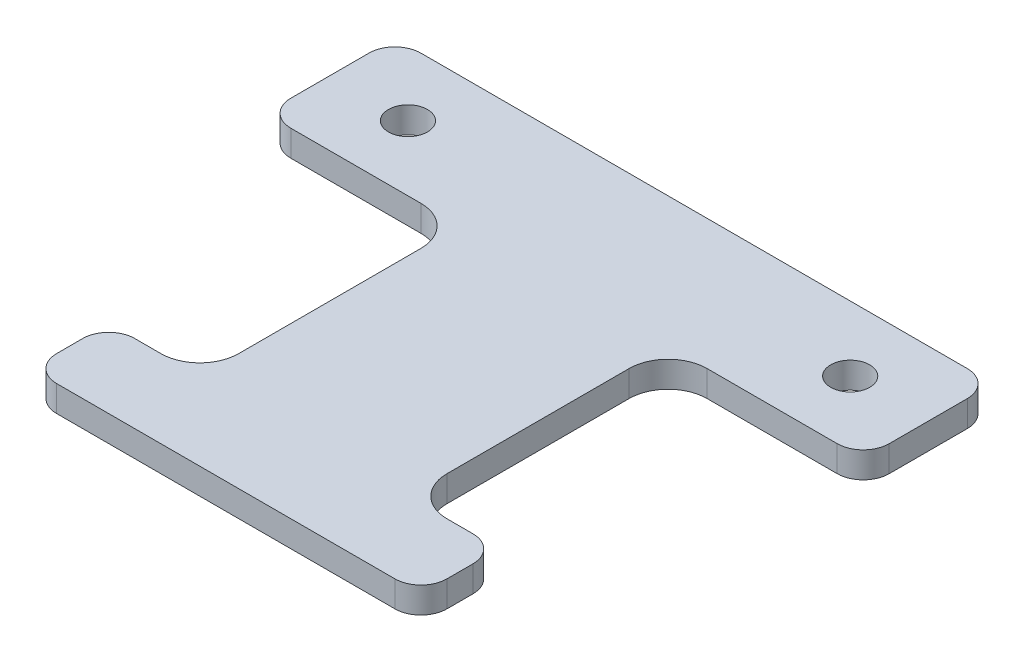
SolidWorks part; units mm, degrees
ref_plane "Vorne" through (0, 0, 0) normal (0, 0, 1) x (1, 0, 0)
ref_plane "Oben" through (0, 0, 0) normal (0, 1, 0) x (1, 0, 0)
ref_plane "Rechts" through (0, 0, 0) normal (1, 0, 0) x (0, 0, -1)
ref_plane "E_Boden" through (0, 1, 0) normal (0, 1, 0) x (1, 0, 0)
sketch "Skizze1" plane through (0, 0, 0) normal (0, 1, 0) x (1, 0, 0)
  line L0 (0, -84.2382) -> (0, 127.1868) construction
  line L1 (-165.4867, 0) -> (188.3198, 0) construction
  line L2 (-105, 90) -> (105, 90)
  line L3 (-115, 80) -> (-115, 50)
  line L8 (-105, 40) -> (-55, 40)
  line L9 (-40, 25) -> (-40, -45)
  line L10 (-55, -60) -> (-65, -60)
  line L11 (-75, -70) -> (-75, -80)
  line L12 (-65, -90) -> (65, -90)
  line L13 (75, -70) -> (75, -80)
  line L14 (55, -60) -> (65, -60)
  line L15 (40, 25) -> (40, -45)
  line L16 (105, 40) -> (55, 40)
  line L17 (115, 80) -> (115, 50)
  arc A0 (40, 25) -> (55, 40) centre (55, 25) cw
  arc A1 (55, -60) -> (40, -45) centre (55, -45) cw
  arc A2 (-40, -45) -> (-55, -60) centre (-55, -45) cw
  arc A3 (-55, 40) -> (-40, 25) centre (-55, 25) cw
  arc A4 (75, -70) -> (65, -60) centre (65, -70) ccw
  arc A5 (75, -80) -> (65, -90) centre (65, -80) cw
  arc A6 (-75, -80) -> (-65, -90) centre (-65, -80) ccw
  arc A7 (-65, -60) -> (-75, -70) centre (-65, -70) ccw
  arc A8 (-115, 50) -> (-105, 40) centre (-105, 50) ccw
  arc A9 (105, 40) -> (115, 50) centre (105, 50) ccw
  arc A10 (115, 80) -> (105, 90) centre (105, 80) ccw
  arc A11 (-105, 90) -> (-115, 80) centre (-105, 80) ccw
  point P15 (0, -90)
  point P16 (0, 90)
  point P22 (40, 40)
  point P25 (40, -60)
  point P28 (-40, -60)
  point P31 (-40, 40)
  point P34 (75, -60)
  point P37 (75, -90)
  point P40 (-75, -90)
  point P43 (-75, -60)
  point P46 (-115, 40)
  point P49 (115, 40)
  point P52 (115, 90)
  point P55 (-115, 90)
  dimension "D7" = 15
  dimension "D8" = 10
  dimension "D1" = 230
  dimension "D2" = 50
  dimension "D3" = 130
  dimension "D4" = 150
  dimension "D5" = 80
  dimension "D6" = 30
extrude "Aufsatz-Linear austragen1" add sketch "Skizze1" along normal blind 10
hole_wizard "Ø15.0 (15) Durchmesser Bohrung1" positions "Skizze6" profile "Skizze7" hole size "Ø15.0" standard "DIN" end condition through all
sketch "Skizze6" plane through (0, 10, 0) normal (0, 1, 0) x (1, 0, 0)
  line L2 (105, 90) -> (-105, 90) construction
  line L3 (0, 90) -> (0, -90) construction
  line L4 (-65, -90) -> (65, -90) construction
  point P0 (-85, 65)
  point P2 (85, 65)
  dimension "D1" = 25
  dimension "D2" = 25
  dimension "D3" = 170
sketch "Skizze7" plane through (-85, 10, -65) normal (1, 0, 0) x (0, 0, 1)
  line L0 (0, 0) -> (0, 10)
  line L1 (0, 10) -> (7.5, 10)
  line L2 (7.5, 10) -> (7.5, 0)
  line L5 (7.5, 0) -> (0, 0)
  line L11 (0, -6.35) -> (0, 107.95) construction
  dimension "Bohrerdurchmesser" = 15
  dimension "Bohrungstiefe" = 10
